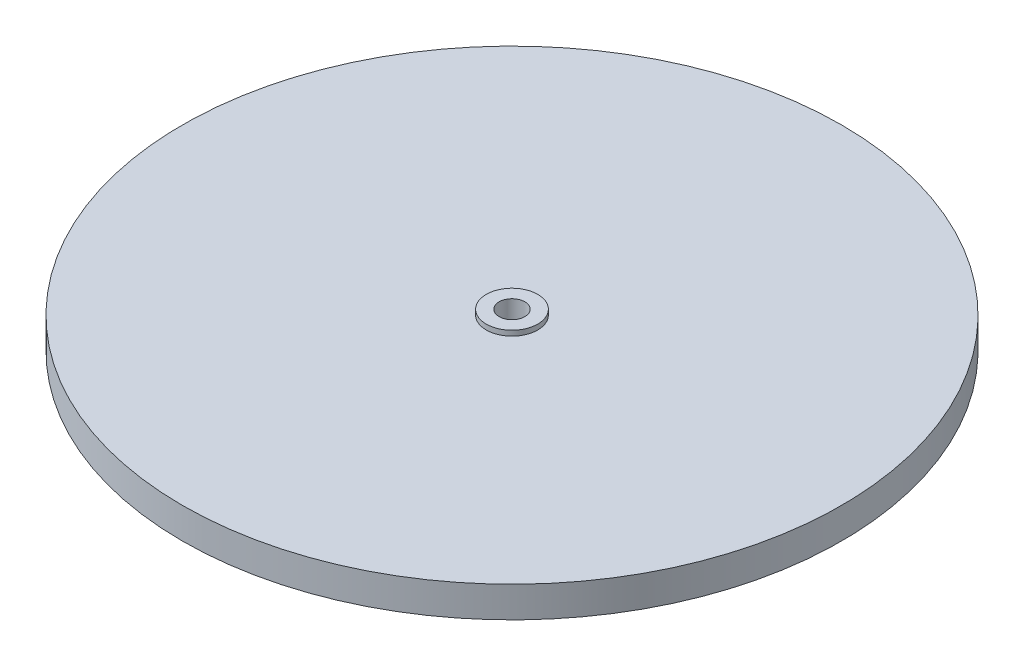
SolidWorks part; units mm, degrees
material "自定义塑料"
ref_plane "前视基准面" through (0, 0, 0) normal (0, 0, 1) x (1, 0, 0)
ref_plane "上视基准面" through (0, 0, 0) normal (0, 1, 0) x (1, 0, 0)
ref_plane "右视基准面" through (0, 0, 0) normal (1, 0, 0) x (0, 0, -1)
sketch "草图1" plane through (0, 0, 0) normal (0, 1, 0) x (1, 0, 0)
  circle A0 centre (0, 0) radius 64
  dimension "D1" = 128
extrude "凸台-拉伸1" add sketch "草图1" along normal blind 3 and the other way blind 3
sketch "草图2" plane through (0, 0, 0) normal (0, 1, 0) x (1, 0, 0)
  circle A0 centre (0, 0) radius 5
  dimension "D1" = 10
extrude "凸台-拉伸2" add sketch "草图2" along normal blind 4 and the other way blind 7
sketch "草图3" plane through (0, 4, 0) normal (0, 1, 0) x (1, 0, 0)
  circle A0 centre (0, 0) radius 2.5
  dimension "D1" = 5
extrude "切除-拉伸1" cut sketch "草图3" against normal through all
